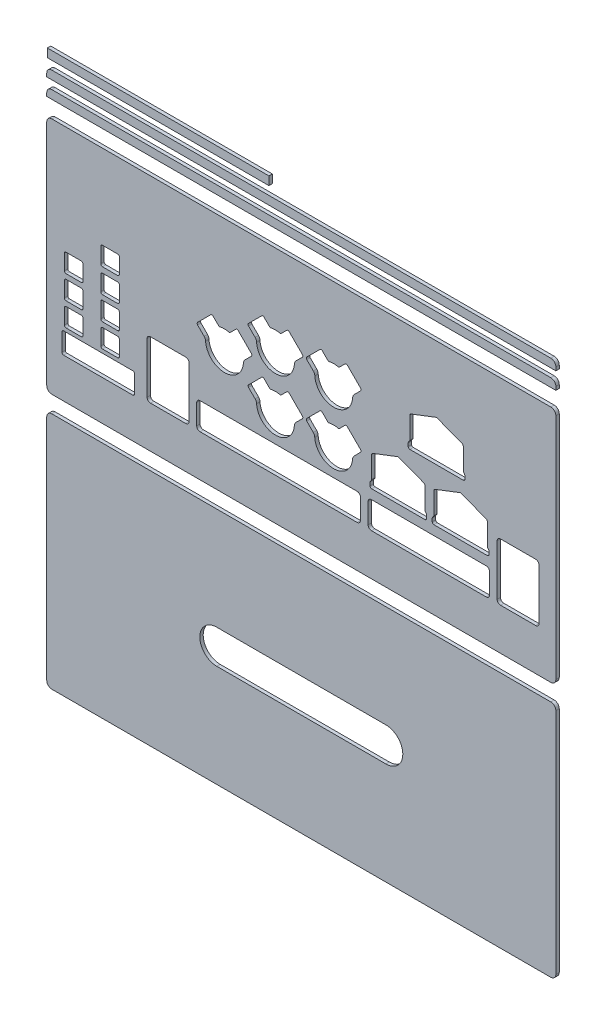
SolidWorks part; units mm, degrees
ref_plane "前视基准面" through (0, 0, 0) normal (0, 0, 1) x (1, 0, 0)
ref_plane "上视基准面" through (0, 0, 0) normal (0, 1, 0) x (1, 0, 0)
ref_plane "右视基准面" through (0, 0, 0) normal (1, 0, 0) x (0, 0, -1)
sketch "草图1" plane through (0, 0, 0) normal (0, 0, 1) x (1, 0, 0)
  line L0 (-5, 136) -> (296, 136)
  line L1 (0, 0) -> (291, 0) construction
  line L2 (0, 0) -> (0, 131) construction
  line L3 (0, 131) -> (291, 131) construction
  line L4 (291, 0) -> (291, 131) construction
  line L5 (296, -5) -> (296, 136)
  line L6 (-5, -5) -> (296, -5)
  line L7 (-5, -5) -> (-5, 136)
  line L8 (146.1106, 88.7345) -> (137.617, 97.2281) construction
  line L9 (137.617, 97.2281) -> (133.4289, 93.0401) construction
  line L10 (126.9441, 93.0401) -> (122.7677, 97.2164) construction
  line L11 (122.7677, 97.2164) -> (114.3461, 88.7948) construction
  line L12 (114.3461, 88.7948) -> (118.5428, 84.5981) construction
  line L13 (146.1106, 88.7345) -> (141.9742, 84.5981) construction
  line L14 (180.5484, 88.7345) -> (172.0548, 97.2281) construction
  line L15 (172.0548, 97.2281) -> (167.8667, 93.0401) construction
  line L16 (161.3819, 93.0401) -> (157.2055, 97.2164) construction
  line L17 (157.2055, 97.2164) -> (148.7839, 88.7948) construction
  line L18 (148.7839, 88.7948) -> (152.9806, 84.5981) construction
  line L19 (180.5484, 88.7345) -> (176.412, 84.5981) construction
  line L20 (180.5022, 57.2605) -> (172.0085, 65.7542) construction
  line L21 (172.0085, 65.7542) -> (167.8205, 61.5662) construction
  line L22 (161.3356, 61.5662) -> (157.1593, 65.7425) construction
  line L23 (157.1593, 65.7425) -> (148.7377, 57.3208) construction
  line L24 (148.7377, 57.3208) -> (152.9344, 53.1241) construction
  line L25 (180.5022, 57.2605) -> (176.3658, 53.1241) construction
  line L26 (146.1106, 57.2605) -> (137.617, 65.7542) construction
  line L27 (137.617, 65.7542) -> (133.4289, 61.5662) construction
  line L28 (126.9441, 61.5662) -> (122.7677, 65.7425) construction
  line L29 (122.7677, 65.7425) -> (114.3461, 57.3208) construction
  line L30 (114.3461, 57.3208) -> (118.5428, 53.1241) construction
  line L31 (146.1106, 57.2605) -> (141.9742, 53.1241) construction
  line L32 (115.973, 74.1947) -> (107.4793, 82.6884) construction
  line L33 (107.4793, 82.6884) -> (103.2913, 78.5004) construction
  line L34 (96.8064, 78.5004) -> (92.6301, 82.6767) construction
  line L35 (92.6301, 82.6767) -> (84.2085, 74.255) construction
  line L36 (84.2085, 74.255) -> (88.4052, 70.0584) construction
  line L37 (115.973, 74.1947) -> (111.8366, 70.0584) construction
  line L38 (107.4793, 83.3955) -> (103.1526, 79.0688)
  line L39 (116.6801, 74.1947) -> (107.4793, 83.3955)
  line L40 (116.6801, 74.1947) -> (112.1901, 69.7048)
  line L41 (83.5014, 74.255) -> (88.0516, 69.7048)
  line L42 (92.6301, 83.3838) -> (83.5014, 74.255)
  line L43 (96.9451, 79.0688) -> (92.6301, 83.3838)
  line L44 (137.617, 97.9352) -> (133.2902, 93.6085)
  line L45 (146.8177, 88.7345) -> (137.617, 97.9352)
  line L46 (146.8177, 88.7345) -> (142.3277, 84.2446)
  line L47 (113.639, 88.7948) -> (118.1893, 84.2446)
  line L48 (122.7677, 97.9236) -> (113.639, 88.7948)
  line L49 (127.0828, 93.6085) -> (122.7677, 97.9236)
  line L50 (172.0548, 97.9352) -> (167.728, 93.6085)
  line L51 (181.2555, 88.7345) -> (172.0548, 97.9352)
  line L52 (181.2555, 88.7345) -> (176.7655, 84.2446)
  line L53 (148.0768, 88.7948) -> (152.6271, 84.2446)
  line L54 (157.2055, 97.9236) -> (148.0768, 88.7948)
  line L55 (161.5206, 93.6085) -> (157.2055, 97.9236)
  line L56 (172.0085, 66.4613) -> (167.6818, 62.1346)
  line L57 (181.2093, 57.2605) -> (172.0085, 66.4613)
  line L58 (181.2093, 57.2605) -> (176.7193, 52.7706)
  line L59 (148.0306, 57.3208) -> (152.5808, 52.7706)
  line L60 (157.1593, 66.4496) -> (148.0306, 57.3208)
  line L61 (161.4743, 62.1346) -> (157.1593, 66.4496)
  line L62 (137.617, 66.4613) -> (133.2902, 62.1346)
  line L63 (146.8177, 57.2605) -> (137.617, 66.4613)
  line L64 (146.8177, 57.2605) -> (142.3277, 52.7706)
  line L65 (113.639, 57.3208) -> (118.1893, 52.7706)
  line L66 (122.7677, 66.4496) -> (113.639, 57.3208)
  line L67 (127.0828, 62.1346) -> (122.7677, 66.4496)
  line L68 (210.1498, 90.4605) -> (225.4449, 96.3518) construction
  line L69 (240.74, 90.4605) -> (225.4449, 96.3518) construction
  line L70 (240.74, 76.8781) -> (240.74, 90.4605) construction
  line L71 (241.6993, 75.6663) -> (240.74, 76.8781) construction
  line L72 (241.6993, 73.1325) -> (241.6993, 75.6663) construction
  line L73 (209.1905, 73.1325) -> (241.6993, 73.1325) construction
  line L74 (209.1905, 73.1325) -> (209.1905, 75.6663) construction
  line L75 (209.1905, 75.6663) -> (210.1498, 76.8781) construction
  line L76 (210.1498, 76.8781) -> (210.1498, 90.4605) construction
  line L77 (241.24, 90.8037) -> (225.4449, 96.8876)
  line L78 (209.6498, 90.8037) -> (225.4449, 96.8876)
  line L79 (209.6498, 77.0521) -> (209.6498, 90.8037)
  line L80 (208.6905, 75.8403) -> (209.6498, 77.0521)
  line L81 (208.6905, 72.6325) -> (208.6905, 75.8403)
  line L82 (208.6905, 72.6325) -> (242.1993, 72.6325)
  line L83 (242.1993, 72.6325) -> (242.1993, 75.8403)
  line L84 (242.1993, 75.8403) -> (241.24, 77.0521)
  line L85 (241.24, 77.0521) -> (241.24, 90.8037)
  line L86 (218.6251, 59.3392) -> (202.83, 65.4231)
  line L87 (187.0349, 59.3392) -> (202.83, 65.4231)
  line L88 (187.0349, 45.5876) -> (187.0349, 59.3392)
  line L89 (186.0756, 44.3758) -> (187.0349, 45.5876)
  line L90 (186.0756, 41.168) -> (186.0756, 44.3758)
  line L91 (186.0756, 41.168) -> (219.5844, 41.168)
  line L92 (219.5844, 41.168) -> (219.5844, 44.3758)
  line L93 (219.5844, 44.3758) -> (218.6251, 45.5876)
  line L94 (218.6251, 45.5876) -> (218.6251, 59.3392)
  line L95 (255.4508, 59.3392) -> (239.6557, 65.4231)
  line L96 (223.8606, 59.3392) -> (239.6557, 65.4231)
  line L97 (223.8606, 45.5876) -> (223.8606, 59.3392)
  line L98 (222.9013, 44.3758) -> (223.8606, 45.5876)
  line L99 (222.9013, 41.168) -> (222.9013, 44.3758)
  line L100 (222.9013, 41.168) -> (256.4101, 41.168)
  line L101 (256.4101, 41.168) -> (256.4101, 44.3758)
  line L102 (256.4101, 44.3758) -> (255.4508, 45.5876)
  line L103 (255.4508, 45.5876) -> (255.4508, 59.3392)
  line L104 (26.937, 60.9701) -> (37.937, 60.9701)
  line L105 (56.3034, 53.6282) -> (77.1351, 53.6282)
  line L106 (54.3034, 51.6282) -> (54.3034, 21.6438)
  line L107 (56.3034, 19.6438) -> (77.1351, 19.6438)
  line L108 (79.1351, 51.6282) -> (79.1351, 21.6438)
  line L109 (85.6411, 35.567) -> (178.4632, 35.567)
  line L110 (83.6411, 33.567) -> (83.6411, 21.6438)
  line L111 (85.6411, 19.6438) -> (178.4632, 19.6438)
  line L112 (180.4632, 33.567) -> (180.4632, 21.6438)
  line L113 (186.9926, 35.567) -> (254.7717, 35.567)
  line L114 (184.9926, 33.567) -> (184.9926, 21.6438)
  line L115 (186.9926, 19.6438) -> (254.7717, 19.6438)
  line L116 (256.7717, 33.567) -> (256.7717, 21.6438)
  line L117 (284.0232, 53.5853) -> (263.2536, 53.5853)
  line L118 (286.0232, 51.5853) -> (286.0232, 21.6438)
  line L119 (284.0232, 19.6438) -> (263.2536, 19.6438)
  line L120 (261.2536, 51.5853) -> (261.2536, 21.6438)
  line L121 (37.937, 71.9701) -> (37.937, 60.9701)
  line L122 (26.937, 71.9701) -> (37.937, 71.9701)
  line L123 (26.937, 71.9701) -> (26.937, 60.9701)
  line L124 (16.437, 71.9701) -> (16.437, 60.9701)
  line L125 (5.437, 60.9701) -> (16.437, 60.9701)
  line L126 (5.437, 71.9701) -> (5.437, 60.9701)
  line L127 (5.437, 71.9701) -> (16.437, 71.9701)
  line L128 (16.437, 58.0701) -> (16.437, 47.0701)
  line L129 (5.437, 47.0701) -> (16.437, 47.0701)
  line L130 (5.437, 58.0701) -> (5.437, 47.0701)
  line L131 (5.437, 58.0701) -> (16.437, 58.0701)
  line L132 (16.437, 44.1701) -> (16.437, 33.1701)
  line L133 (5.437, 33.1701) -> (16.437, 33.1701)
  line L134 (5.437, 44.1701) -> (5.437, 33.1701)
  line L135 (5.437, 44.1701) -> (16.437, 44.1701)
  line L136 (37.937, 58.0701) -> (37.937, 47.0701)
  line L137 (26.937, 47.0701) -> (37.937, 47.0701)
  line L138 (26.937, 58.0701) -> (26.937, 47.0701)
  line L139 (26.937, 58.0701) -> (37.937, 58.0701)
  line L140 (37.937, 44.1701) -> (37.937, 33.1701)
  line L141 (26.937, 33.1701) -> (37.937, 33.1701)
  line L142 (26.937, 44.1701) -> (26.937, 33.1701)
  line L143 (26.937, 44.1701) -> (37.937, 44.1701)
  line L144 (26.937, 75.277) -> (37.937, 75.277)
  line L145 (37.937, 86.277) -> (37.937, 75.277)
  line L146 (26.937, 86.277) -> (37.937, 86.277)
  line L147 (26.937, 86.277) -> (26.937, 75.277)
  line L149 (3.9555, 30.9874) -> (46.8376, 30.9874)
  line L150 (3.9555, 30.9874) -> (3.9555, 18.524)
  line L151 (3.9555, 18.524) -> (46.8376, 18.524)
  line L152 (46.8376, 30.9874) -> (46.8376, 18.524)
  arc A0 (126.9441, 93.0401) -> (133.4289, 93.0401) centre (130.1865, 83.2994) cw construction
  arc A1 (118.5428, 84.5981) -> (119.5465, 82.1745) centre (116.1197, 82.175) cw construction
  arc A2 (119.5465, 82.1745) -> (140.9083, 82.1745) centre (130.2274, 82.9011) ccw construction
  arc A3 (141.9742, 84.5981) -> (140.9083, 82.1745) centre (144.5556, 82.0167) ccw construction
  arc A4 (161.3819, 93.0401) -> (167.8667, 93.0401) centre (164.6243, 83.2994) cw construction
  arc A5 (152.9806, 84.5981) -> (153.9843, 82.1745) centre (150.5575, 82.175) cw construction
  arc A6 (153.9843, 82.1745) -> (175.3461, 82.1745) centre (164.6652, 82.9011) ccw construction
  arc A7 (176.412, 84.5981) -> (175.3461, 82.1745) centre (178.9934, 82.0167) ccw construction
  arc A8 (161.3356, 61.5662) -> (167.8205, 61.5662) centre (164.5781, 51.8254) cw construction
  arc A9 (152.9344, 53.1241) -> (153.9381, 50.7005) centre (150.5113, 50.701) cw construction
  arc A10 (153.9381, 50.7005) -> (175.2999, 50.7005) centre (164.619, 51.4271) ccw construction
  arc A11 (176.3658, 53.1241) -> (175.2999, 50.7005) centre (178.9472, 50.5427) ccw construction
  arc A12 (126.9441, 61.5662) -> (133.4289, 61.5662) centre (130.1865, 51.8254) cw construction
  arc A13 (118.5428, 53.1241) -> (119.5465, 50.7005) centre (116.1197, 50.701) cw construction
  arc A14 (119.5465, 50.7005) -> (140.9083, 50.7005) centre (130.2274, 51.4271) ccw construction
  arc A15 (141.9742, 53.1241) -> (140.9083, 50.7005) centre (144.5556, 50.5427) ccw construction
  arc A16 (96.8064, 78.5004) -> (103.2913, 78.5004) centre (100.0489, 68.7596) cw construction
  arc A17 (88.4052, 70.0584) -> (89.4089, 67.6348) centre (85.9821, 67.6352) cw construction
  arc A18 (89.4089, 67.6348) -> (110.7707, 67.6348) centre (100.0898, 68.3613) ccw construction
  arc A19 (111.8366, 70.0584) -> (110.7707, 67.6348) centre (114.418, 67.4769) ccw construction
  arc A20 (96.9451, 79.0688) -> (103.1526, 79.0688) centre (100.0489, 68.7596) cw
  arc A21 (112.1901, 69.7048) -> (111.27, 67.6073) centre (114.418, 67.4769) ccw
  arc A22 (88.9088, 67.6187) -> (111.27, 67.6073) centre (100.0898, 68.3613) ccw
  arc A23 (88.0516, 69.7048) -> (88.9088, 67.6187) centre (85.9821, 67.6352) cw
  arc A24 (127.0828, 93.6085) -> (133.2902, 93.6085) centre (130.1865, 83.2994) cw
  arc A25 (142.3277, 84.2446) -> (141.4076, 82.147) centre (144.5556, 82.0167) ccw
  arc A26 (119.0465, 82.1584) -> (141.4076, 82.147) centre (130.2274, 82.9011) ccw
  arc A27 (118.1893, 84.2446) -> (119.0465, 82.1584) centre (116.1197, 82.175) cw
  arc A28 (161.5206, 93.6085) -> (167.728, 93.6085) centre (164.6243, 83.2994) cw
  arc A29 (176.7655, 84.2446) -> (175.8454, 82.147) centre (178.9934, 82.0167) ccw
  arc A30 (153.4843, 82.1584) -> (175.8454, 82.147) centre (164.6652, 82.9011) ccw
  arc A31 (152.6271, 84.2446) -> (153.4843, 82.1584) centre (150.5575, 82.175) cw
  arc A32 (161.4743, 62.1346) -> (167.6818, 62.1346) centre (164.5781, 51.8254) cw
  arc A33 (176.7193, 52.7706) -> (175.7992, 50.6731) centre (178.9472, 50.5427) ccw
  arc A34 (153.438, 50.6845) -> (175.7992, 50.6731) centre (164.619, 51.4271) ccw
  arc A35 (152.5808, 52.7706) -> (153.438, 50.6845) centre (150.5113, 50.701) cw
  arc A36 (127.0828, 62.1346) -> (133.2902, 62.1346) centre (130.1865, 51.8254) cw
  arc A37 (142.3277, 52.7706) -> (141.4076, 50.6731) centre (144.5556, 50.5427) ccw
  arc A38 (119.0465, 50.6845) -> (141.4076, 50.6731) centre (130.2274, 51.4271) ccw
  arc A39 (118.1893, 52.7706) -> (119.0465, 50.6845) centre (116.1197, 50.701) cw
  arc A40 (286.0232, 21.6438) -> (284.0232, 19.6438) centre (284.0232, 21.6438) cw
  arc A41 (284.0232, 53.5853) -> (286.0232, 51.5853) centre (284.0232, 51.5853) cw
  arc A42 (263.2536, 53.5853) -> (261.2536, 51.5853) centre (263.2536, 51.5853) ccw
  arc A43 (263.2536, 19.6438) -> (261.2536, 21.6438) centre (263.2536, 21.6438) cw
  arc A44 (254.7717, 19.6438) -> (256.7717, 21.6438) centre (254.7717, 21.6438) ccw
  arc A45 (254.7717, 35.567) -> (256.7717, 33.567) centre (254.7717, 33.567) cw
  arc A46 (186.9926, 35.567) -> (184.9926, 33.567) centre (186.9926, 33.567) ccw
  arc A47 (184.9926, 21.6438) -> (186.9926, 19.6438) centre (186.9926, 21.6438) ccw
  arc A48 (178.4632, 19.6438) -> (180.4632, 21.6438) centre (178.4632, 21.6438) ccw
  arc A49 (178.4632, 35.567) -> (180.4632, 33.567) centre (178.4632, 33.567) cw
  arc A50 (83.6411, 21.6438) -> (85.6411, 19.6438) centre (85.6411, 21.6438) ccw
  arc A51 (85.6411, 35.567) -> (83.6411, 33.567) centre (85.6411, 33.567) ccw
  arc A52 (77.1351, 19.6438) -> (79.1351, 21.6438) centre (77.1351, 21.6438) ccw
  arc A53 (54.3034, 21.6438) -> (56.3034, 19.6438) centre (56.3034, 21.6438) ccw
  arc A54 (77.1351, 53.6282) -> (79.1351, 51.6282) centre (77.1351, 51.6282) cw
  arc A55 (56.3034, 53.6282) -> (54.3034, 51.6282) centre (56.3034, 51.6282) ccw
  dimension "D10" = 2
  dimension "D1" = 131
  dimension "D2" = 291
  dimension "D3" = 5
  dimension "D4" = 0.5
  dimension "D5" = 0.5
  dimension "D6" = 0.5
  dimension "D7" = 0.5
  dimension "D8" = 0.5
  dimension "D9" = 0.5
  dimension "D11" = 2
  dimension "D12" = 3
extrude "凸台-拉伸1" add sketch "草图1" against normal blind 2
fillet "圆角1" radius 3 4 edges at (296, 136, -1) (296, -5, -1) (-5, -5, -1) (-5, 136, -1)
fillet "圆角2" radius 1 99 edges at (103.1526, 79.0688, -1) (107.4793, 83.3955, -1) (116.6801, 74.1947, -1) (111.27, 67.6073, -1) (88.9088, 67.6187, -1) (83.5014, 74.255, -1) (92.6301, 83.3838, -1) (96.9451, 79.0688, -1) (133.2902, 93.6085, -1) (137.617, 97.9352, -1) (146.8177, 88.7345, -1) (141.4076, 82.147, -1) (119.0465, 82.1584, -1) (113.639, 88.7948, -1) (122.7677, 97.9236, -1) (127.0828, 93.6085, -1) (167.728, 93.6085, -1) (172.0548, 97.9352, -1) (181.2555, 88.7345, -1) (175.8454, 82.147, -1) (153.4843, 82.1584, -1) (148.0768, 88.7948, -1) (157.2055, 97.9236, -1) (161.5206, 93.6085, -1) (167.6818, 62.1346, -1) (172.0085, 66.4613, -1) (181.2093, 57.2605, -1) (175.7992, 50.6731, -1) (153.438, 50.6845, -1) (148.0306, 57.3208, -1) (157.1593, 66.4496, -1) (161.4743, 62.1346, -1) (133.2902, 62.1346, -1) (137.617, 66.4613, -1) (146.8177, 57.2605, -1) (141.4076, 50.6731, -1) (119.0465, 50.6845, -1) (113.639, 57.3208, -1) (122.7677, 66.4496, -1) (127.0828, 62.1346, -1) (241.24, 77.0521, -1) (242.1993, 75.8403, -1) (242.1993, 72.6325, -1) (208.6905, 72.6325, -1) (208.6905, 75.8403, -1) (209.6498, 77.0521, -1) (209.6498, 90.8037, -1) (225.4449, 96.8876, -1) (241.24, 90.8037, -1) (218.6251, 45.5876, -1) (219.5844, 44.3758, -1) (219.5844, 41.168, -1) (186.0756, 41.168, -1) (186.0756, 44.3758, -1) (187.0349, 45.5876, -1) (187.0349, 59.3392, -1) (202.83, 65.4231, -1) (218.6251, 59.3392, -1) (255.4508, 45.5876, -1) (256.4101, 44.3758, -1) (256.4101, 41.168, -1) (222.9013, 41.168, -1) (222.9013, 44.3758, -1) (223.8606, 45.5876, -1) (223.8606, 59.3392, -1) (239.6557, 65.4231, -1) (255.4508, 59.3392, -1) (26.937, 71.9701, -1) (37.937, 71.9701, -1) (37.937, 60.9701, -1) (26.937, 60.9701, -1) (26.937, 86.277, -1) (37.937, 86.277, -1) (37.937, 75.277, -1) (26.937, 75.277, -1) (16.437, 71.9701, -1) (16.437, 60.9701, -1) (5.437, 60.9701, -1) (16.437, 58.0701, -1) (16.437, 47.0701, -1) (5.437, 47.0701, -1) (5.437, 58.0701, -1) (16.437, 44.1701, -1) (16.437, 33.1701, -1) (5.437, 33.1701, -1) (5.437, 44.1701, -1) (37.937, 58.0701, -1) (37.937, 47.0701, -1) (26.937, 47.0701, -1) (26.937, 58.0701, -1) (37.937, 44.1701, -1) (37.937, 33.1701, -1) (26.937, 33.1701, -1) (26.937, 44.1701, -1) (3.9555, 30.9874, -1) (46.8376, 30.9874, -1) (46.8376, 18.524, -1) (3.9555, 18.524, -1) (5.437, 71.9701, -1)
sketch "草图2" plane through (0, 0, 0) normal (0, 0, 1) x (1, 0, 0)
  line L0 (293, 136) -> (-2, 136) construction
  line L1 (-5, 146) -> (296, 146)
  line L2 (-5, 146) -> (-5, 151)
  line L3 (-5, 151) -> (296, 151)
  line L4 (296, 146) -> (296, 151)
  line L5 (-5, 133) -> (-5, -2) construction
  line L6 (296, -2) -> (296, 133) construction
  dimension "D1" = 10
  dimension "D2" = 5
extrude "凸台-拉伸2" add sketch "草图2" against normal blind 2 separate body
fillet "圆角3" radius 3 2 edges at (-5, 151, -1) (296, 151, -1)
pattern_linear "阵列(线性)1" count 2 spacing 10 along (0, 1, 0) of bodies 107
sketch "草图3" plane through (0, 0, 0) normal (0, 0, 1) x (1, 0, 0)
  line L0 (293, 161) -> (-2, 161) construction
  line L1 (-4.6377, 166) -> (126.3623, 166)
  line L2 (-4.6377, 166) -> (-4.6377, 171)
  line L3 (-4.6377, 171) -> (126.3623, 171)
  line L4 (126.3623, 166) -> (126.3623, 171)
  dimension "D1" = 131
  dimension "D2" = 5
  dimension "D3" = 5
extrude "凸台-拉伸3" add sketch "草图3" against normal blind 2 separate body
sketch "草图4" plane through (0, 0, 0) normal (0, 0, 1) x (1, 0, 0)
  line L0 (-5, 133) -> (-5, -2) construction
  line L1 (-5, -15) -> (296, -15)
  line L2 (-5, -15) -> (-5, -156)
  line L3 (-5, -156) -> (296, -156)
  line L4 (296, -15) -> (296, -156)
  line L5 (-2, -5) -> (293, -5) construction
  dimension "D1" = 141
  dimension "D2" = 301
  dimension "D3" = 10
extrude "凸台-拉伸4" add sketch "草图4" against normal blind 2 separate body
fillet "圆角4" radius 3 4 edges at (-5, -156, -1) (296, -156, -1) (296, -15, -1) (-5, -15, -1)
sketch "草图6" plane through (0, 0, 0) normal (0, 0, 1) x (1, 0, 0)
  line L0 (95.5, -85.5) -> (195.5, -85.5) construction
  line L1 (95.5, -75.5) -> (195.5, -75.5)
  line L2 (95.5, -95.5) -> (195.5, -95.5)
  line L6 (95.5, -85.5) -> (-5, -85.5) construction
  line L7 (-5, -18) -> (-5, -153) construction
  line L8 (195.5, -85.5) -> (296, -85.5) construction
  line L9 (296, -153) -> (296, -18) construction
  line L10 (195.5, -85.5) -> (195.5, -15) construction
  line L11 (293, -15) -> (-2, -15) construction
  line L12 (195.5, -85.5) -> (195.5, -156) construction
  line L13 (-2, -156) -> (293, -156) construction
  arc A0 (95.5, -75.5) -> (95.5, -95.5) centre (95.5, -85.5) ccw
  arc A1 (195.5, -95.5) -> (195.5, -75.5) centre (195.5, -85.5) ccw
  point P2 (145.5, -85.5)
  dimension "D1" = 10
  dimension "D2" = 100
extrude "切除-拉伸1" cut sketch "草图6" against normal blind 2
